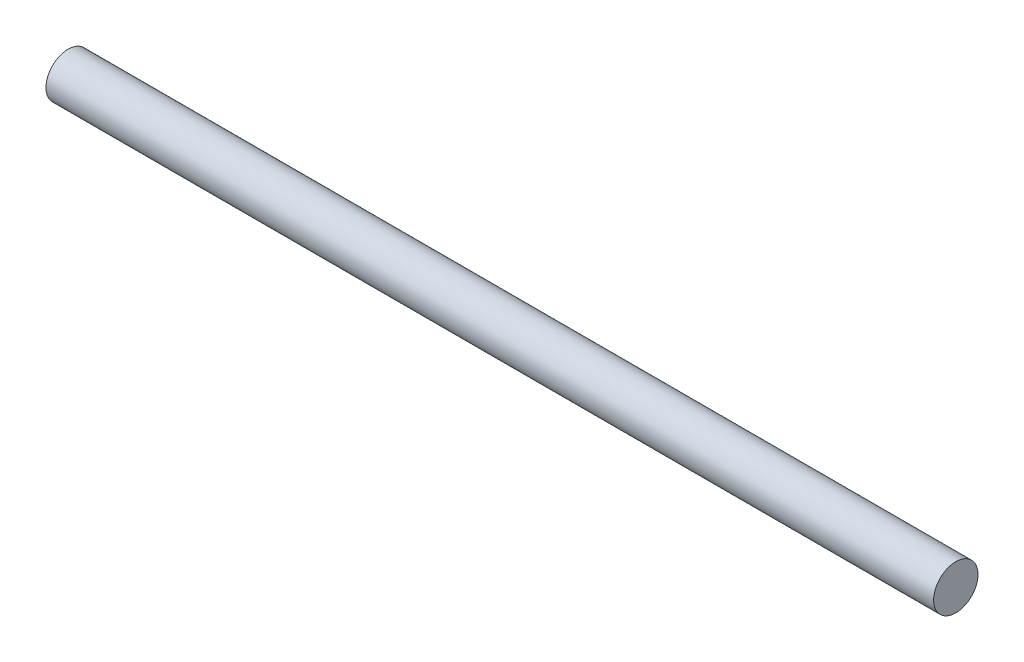
SolidWorks part; units mm, degrees
material "Plain Carbon Steel"
ref_plane "Front Plane" through (0, 0, 0) normal (0, 0, 1) x (1, 0, 0)
ref_plane "Top Plane" through (0, 0, 0) normal (0, 1, 0) x (1, 0, 0)
ref_plane "Right Plane" through (0, 0, 0) normal (1, 0, 0) x (0, 0, -1)
sketch "Sketch1" plane through (0, 0, 0) normal (1, 0, 0) x (0, 0, -1)
  circle A0 centre (0, 0) radius 3.175
  dimension "D1" = 6.35
extrude "Boss-Extrude1" add sketch "Sketch1" along normal blind 127
